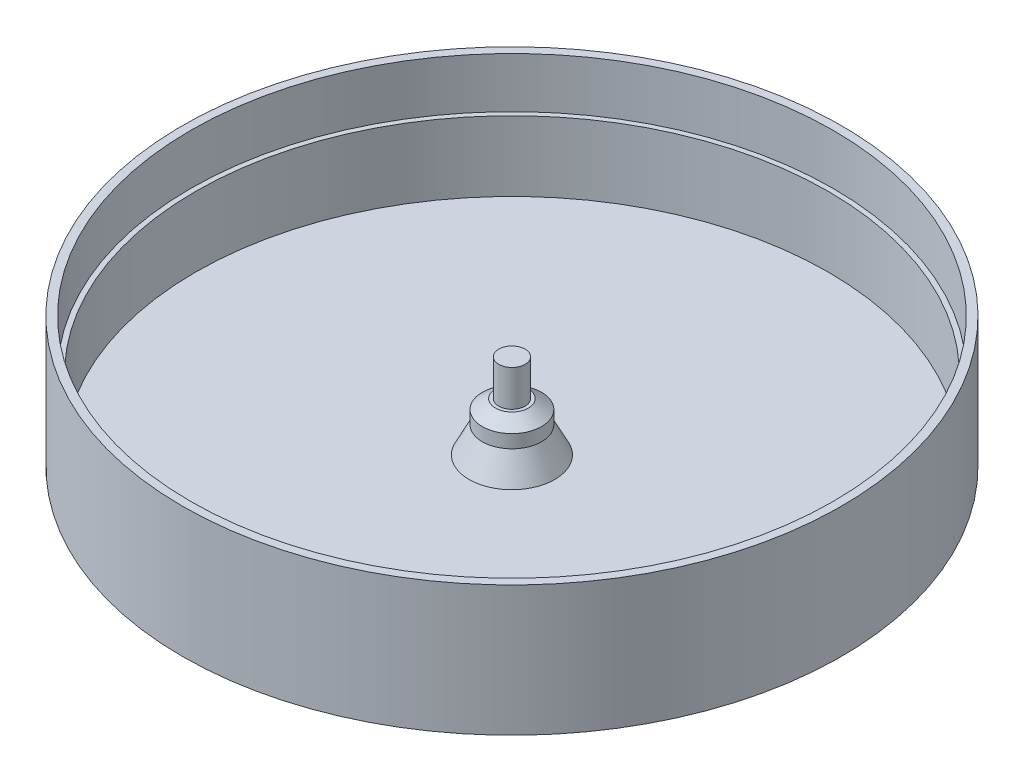
SolidWorks part; units mm, degrees
ref_plane "Front Plane" through (0, 0, 0) normal (0, 0, 1) x (1, 0, 0)
ref_plane "Top Plane" through (0, 0, 0) normal (0, 1, 0) x (1, 0, 0)
ref_plane "Right Plane" through (0, 0, 0) normal (1, 0, 0) x (0, 0, -1)
sketch "Sketch1" plane through (0, 0, 0) normal (0, 1, 0) x (1, 0, 0)
  circle A0 centre (0, 0) radius 100
  circle A1 centre (0, 0) radius 97.5
  circle A2 centre (0, 0) radius 96
extrude "Boss-Extrude1" add sketch "Sketch1" along normal blind 3 contours A2 region at (0, 0, 0)
extrude "Boss-Extrude2" add sketch "Sketch1<4>" along normal blind 24.22 contours A1 A2 region at (-97.2242, 0, 0)
sketch "Sketch1<4>" plane through (0, 0, 0) normal (0, 1, 0) x (1, 0, 0) same geometry as "Sketch1"
extrude "Boss-Extrude3" add sketch "Sketch1<5>" along normal blind 39.5 contours A0 A1 region at (-99.7172, 0, 0)
sketch "Sketch1<5>" plane through (0, 0, 0) normal (0, 1, 0) x (1, 0, 0) same geometry as "Sketch1"
sketch "Sketch5" plane through (0, 3, 0) normal (0, 1, 0) x (1, 0, 0)
  line L0 (0, 96) -> (0, -100) construction
  circle A0 centre (0, 0) radius 96 construction
  circle A1 centre (0, 0) radius 100 construction
  point P0 (0, 0)
ref_plane "Plane1" through (0, 3, 0) normal (0, 0, 1) x (1, 0, 0)
sketch "Sketch6" plane through (0, 3, 0) normal (0, 0, 1) x (1, 0, 0)
  line L0 (0, 0) -> (-13, 0)
  line L1 (-13, 0) -> (-9, 7.9188)
  line L2 (-9, 7.9188) -> (-9, 11.9188)
  line L3 (-9, 11.9188) -> (-5, 14.7685)
  line L4 (-5, 14.7685) -> (-4, 14.7685)
  line L5 (-4, 14.7685) -> (-4, 25.7685)
  line L6 (-4, 25.7685) -> (0, 25.7685)
  line L7 (0, 25.7685) -> (0, 0)
  line L8 (0, 29.4112) -> (0, -20.6061) construction
  dimension "D1" = 13
  dimension "D2" = 9
  dimension "D3" = 4
  dimension "D4" = 5
  dimension "D5" = 4
revolve "Revolve1" add sketch "Sketch6" angle 360 about L8
